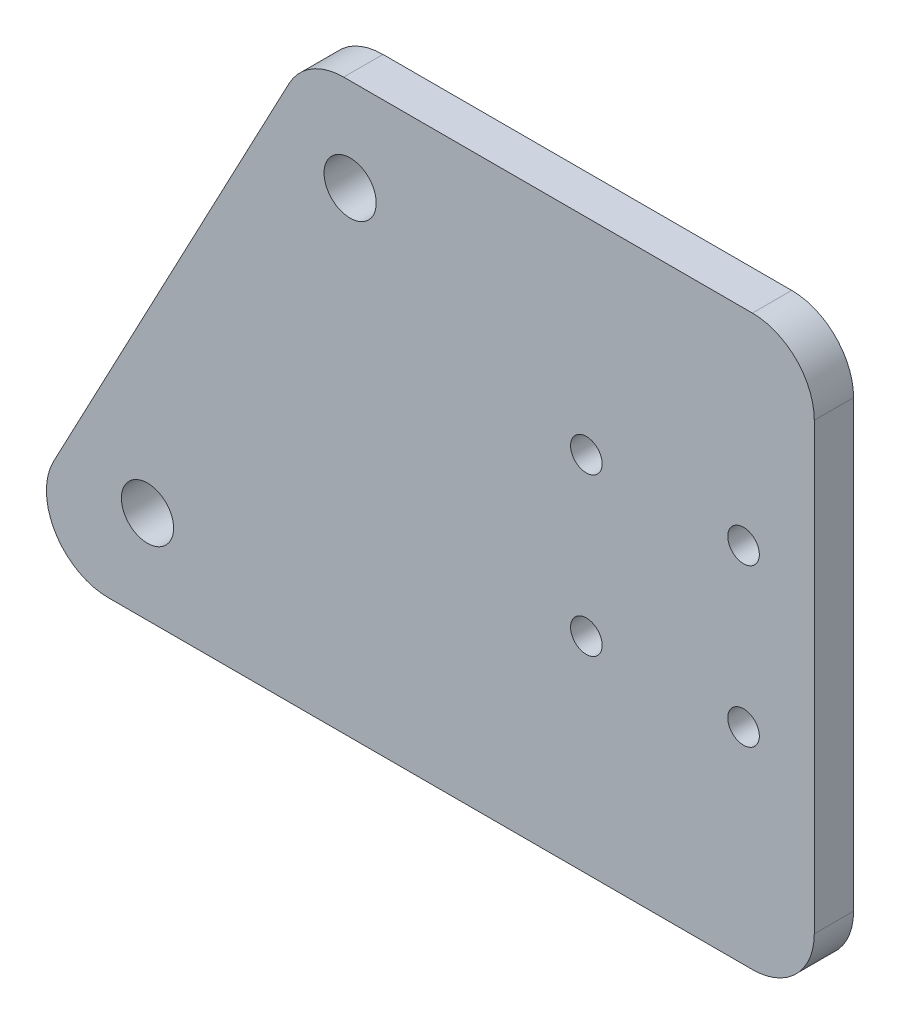
SolidWorks part; units mm, degrees
material "PC High Viscosity"
ref_plane "Front Plane" through (0, 0, 0) normal (0, 0, 1) x (1, 0, 0)
ref_plane "Top Plane" through (0, 0, 0) normal (0, 1, 0) x (1, 0, 0)
ref_plane "Right Plane" through (0, 0, 0) normal (1, 0, 0) x (0, 0, -1)
ref_axis "Axis1" through (0, -55, 0) along (0, 1, 0)
sketch "Sketch1" plane through (0, 0, 0) normal (0, 0, 1) x (1, 0, 0)
  line L0 (267.9385, -135) -> (219.318, -226.8697)
  line L2 (267.9385, -135) -> (350, -135)
  line L3 (350, -135) -> (350, -226.8697)
  line L4 (350, -226.8697) -> (219.318, -226.8697)
  line L5 (275, -150) -> (260, -150) construction
  line L6 (275, -150) -> (275, -135) construction
  line L7 (242.2565, -211.8697) -> (242.2565, -226.8697) construction
  circle A2 centre (275, -150) radius 3.175 construction
  circle A3 centre (242.2565, -211.8697) radius 3.175 construction
  circle A4 centre (275, -150) radius 4.2164
  circle A5 centre (242.2565, -211.8697) radius 4.2164
  dimension "D5" = 8.4328
  dimension "D2" = 15
  dimension "D3" = 15
  dimension "D4" = 15
extrude "Boss-Extrude1" add sketch "Sketch1" along normal blind 6.35
sketch "Sketch2" plane through (0, 0, 6.35) normal (0, 0, 1) x (1, 0, 0)
  line L0 (350, -226.8697) -> (350, -135) construction
  line L1 (313.17, -193.6349) -> (338.57, -193.6349) construction
  line L2 (313.17, -193.6349) -> (313.17, -168.2349) construction
  line L3 (313.17, -168.2349) -> (338.57, -168.2349) construction
  line L4 (338.57, -193.6349) -> (338.57, -168.2349) construction
  line L5 (313.17, -193.6349) -> (338.57, -168.2349) construction
  line L6 (313.17, -168.2349) -> (338.57, -193.6349) construction
  line L7 (350, -180.9349) -> (338.57, -180.9349) construction
  circle A0 centre (313.17, -168.2349) radius 2.5527
  circle A1 centre (338.57, -168.2349) radius 2.5527
  circle A2 centre (313.17, -193.6349) radius 2.5527
  circle A3 centre (338.57, -193.6349) radius 2.5527
  point P0 (325.87, -180.9349)
  dimension "D4" = 5.1054
  dimension "D1" = 25.4
  dimension "D2" = 25.4
  dimension "D3" = 11.43
extrude "Cut-Extrude1" cut sketch "Sketch2" against normal blind 6.35
fillet "Fillet1" radius 10 4 edges at (267.9385, -135, 3.175) (219.318, -226.8697, 3.175) (350, -226.8697, 3.175) (350, -135, 3.175)
